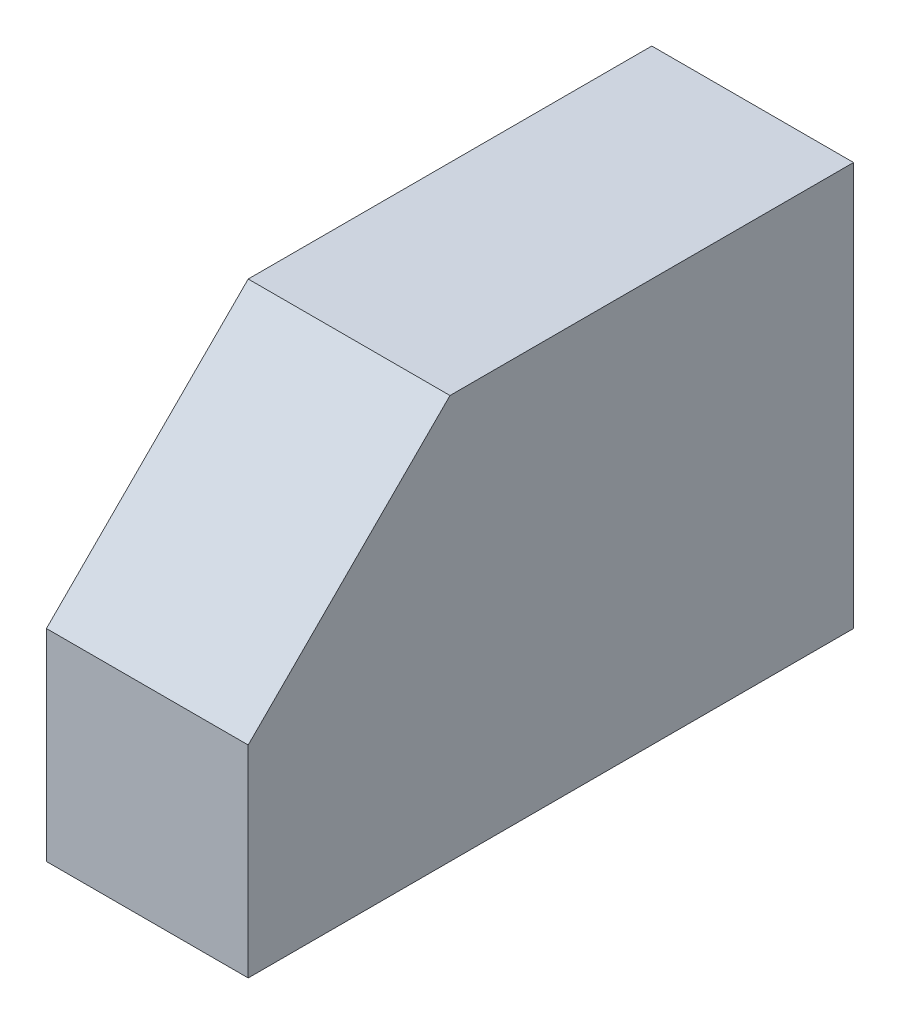
SolidWorks part; units mm, degrees
ref_plane "Front Plane" through (0, 0, 0) normal (0, 0, 1) x (1, 0, 0)
ref_plane "Top Plane" through (0, 0, 0) normal (0, 1, 0) x (1, 0, 0)
ref_plane "Right Plane" through (0, 0, 0) normal (1, 0, 0) x (0, 0, -1)
sketch "Sketch2" plane through (0, 0, 0) normal (0, 0, 1) x (1, 0, 0)
  line L1 (-25, 50) -> (25, 50)
  line L2 (-25, 50) -> (-25, -50)
  line L3 (-25, -50) -> (25, -50)
  line L4 (25, 50) -> (25, -50)
  dimension "block_length" = 50
  dimension "D1" = 25
  dimension "D2" = 50
  dimension "block_width" = 100
extrude "Boss-Extrude1" add sketch "Sketch2" along normal blind 150
sketch "Sketch3" plane through (-25, 0, 0) normal (-1, 0, 0) x (0, 0, 1)
  line L5 (100, 50) -> (150, 0)
  line L6 (150, 50) -> (0, 50) construction
  line L7 (150, 50) -> (150, -50) construction
  line L8 (150, 0) -> (150, 50)
  line L9 (150, 50) -> (100, 50)
  dimension "D1" = 45
  dimension "D2" = 50
extrude "Cut-Extrude1" cut sketch "Sketch3" against normal blind 150
ref_axis "Axis1" through (0, 0, 157.5) along (0, 0, -1)
equation "\"D1@Sketch2\" = \"block_length@Sketch2\" / 2"
equation "\"D2@Sketch2\"=\"block_width@Sketch2\"/2"
